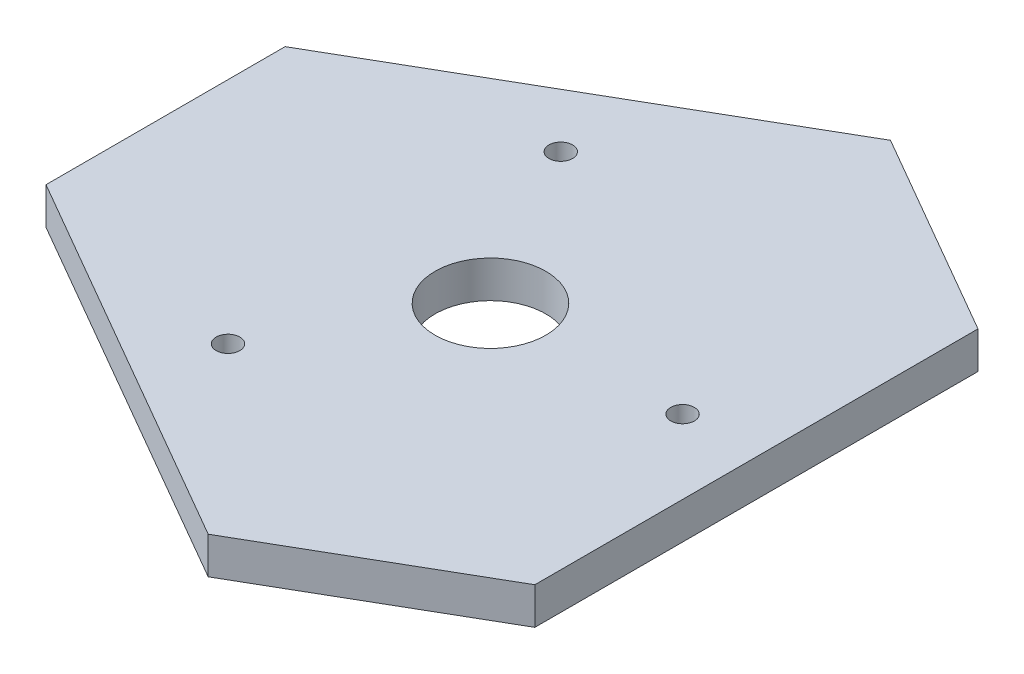
SolidWorks part; units mm, degrees
ref_plane "Front Plane" through (0, 0, 0) normal (0, 0, 1) x (1, 0, 0)
ref_plane "Top Plane" through (0, 0, 0) normal (0, 1, 0) x (1, 0, 0)
ref_plane "Right Plane" through (0, 0, 0) normal (1, 0, 0) x (0, 0, -1)
sketch "Sketch2" plane through (0, 0, 0) normal (0, 1, 0) x (1, 0, 0)
  line L0 (0, 0) -> (-43656.8426, 0) construction
  line L1 (22.8681, 19.05) -> (22.8681, -19.05)
  line L2 (22.8681, 39.6088) -> (-45.7363, 0) construction
  line L3 (-45.7363, 0) -> (22.8681, -39.6088) construction
  line L4 (22.8681, -39.6088) -> (22.8681, 39.6088) construction
  line L5 (22.8681, -19.05) -> (5.0637, -29.3294)
  line L6 (5.0637, -29.3294) -> (-27.9319, -10.2794)
  line L7 (-0.0355, 0.0615) -> (21828.3858, -37807.8732) construction
  line L8 (40.0162, 69.3101) -> (-21788.4051, -37738.6247) construction
  line L9 (-27.9319, -10.2794) -> (-27.9319, 10.2794)
  line L10 (-27.9319, 10.2794) -> (5.0637, 29.3294)
  line L11 (5.0637, 29.3294) -> (22.8681, 19.05)
  circle A0 centre (0, 0) radius 45.7363 construction
  circle A1 centre (16.5181, 0) radius 1.016
  circle A2 centre (-8.2591, -14.3051) radius 1.016
  circle A3 centre (-8.2591, 14.3051) radius 1.016
  circle A4 centre (0, 0) radius 4.7625
  dimension "D2" = 2.032
  dimension "D3" = 9.525
  dimension "D1" = 38.1
  dimension "D4" = 3
  dimension "D5" = 6.35
  dimension "D6" = 50.8
extrude "Boss-Extrude2" add sketch "Sketch2" along normal blind 3.175
